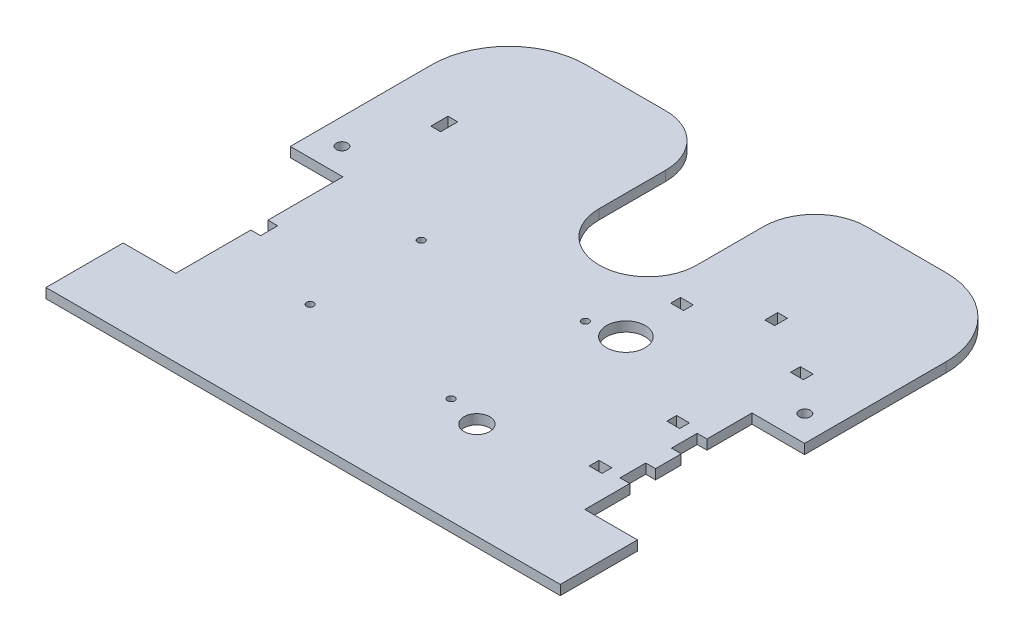
SolidWorks part; units mm, degrees
ref_plane "Front Plane" through (0, 0, 0) normal (0, 0, 1) x (1, 0, 0)
ref_plane "Top Plane" through (0, 0, 0) normal (0, 1, 0) x (1, 0, 0)
ref_plane "Right Plane" through (0, 0, 0) normal (1, 0, 0) x (0, 0, -1)
sketch "Sketch1" plane through (0, 0, 0) normal (0, 1, 0) x (1, 0, 0)
  line L1 (-127, 114.3) -> (127, 114.3)
  line L2 (-127, 114.3) -> (-127, -114.3)
  line L3 (-127, -114.3) -> (127, -114.3)
  line L4 (127, 114.3) -> (127, -114.3)
  line L5 (-127, 114.3) -> (127, -114.3) construction
  line L6 (-127, -114.3) -> (127, 114.3) construction
  point P0 (0, 0)
  dimension "D1" = 254
  dimension "D2" = 228.6
extrude "Boss-Extrude1" add sketch "Sketch1" along normal blind 4.826
sketch "Sketch2" plane through (0, 4.826, 0) normal (0, 1, 0) x (1, 0, 0)
  line L0 (-127, 114.3) -> (-127, -114.3) construction
  line L1 (-127, 6.35) -> (-101, 6.35)
  line L2 (-127, 6.35) -> (-127, -76.2)
  line L3 (-127, -76.2) -> (-101, -76.2)
  line L4 (-101, 6.35) -> (-101, -76.2)
  line L5 (127, -114.3) -> (127, 114.3) construction
  line L6 (127, 6.35) -> (101, 6.35)
  line L7 (127, 6.35) -> (127, -76.2)
  line L8 (127, -76.2) -> (101, -76.2)
  line L9 (101, 6.35) -> (101, -76.2)
  line L10 (-127, -114.3) -> (127, -114.3) construction
  dimension "D1" = 38.1
  dimension "D2" = 38.1
  dimension "D3" = 82.55
  dimension "D4" = 82.55
  dimension "D5" = 26
  dimension "D6" = 26
extrude "Cut-Extrude1" cut sketch "Sketch2" against normal blind 4.826
sketch "Sketch4" plane through (0, 4.826, 0) normal (0, 1, 0) x (1, 0, 0)
  line L0 (0, -114.3) -> (0, 114.3) construction
  line L1 (-127, -114.3) -> (127, -114.3) construction
  line L2 (127, 114.3) -> (-127, 114.3) construction
  line L3 (-127, 76.2) -> (-88.9, 76.2) construction
  line L4 (-127, 114.3) -> (-127, 6.35) construction
  line L5 (-88.9, 76.2) -> (-88.9, 114.3) construction
  line L6 (-127, 76.2) -> (-127, 114.3)
  line L7 (-127, 114.3) -> (-88.9, 114.3)
  line L8 (127, 76.2) -> (127, 114.3)
  line L9 (127, 114.3) -> (88.9, 114.3)
  arc A0 (-127, 76.2) -> (-88.9, 114.3) centre (-88.9, 76.2) cw
  arc A1 (127, 76.2) -> (88.9, 114.3) centre (88.9, 76.2) ccw
  dimension "D1" = 38.1
  dimension "D2" = 38.1
extrude "Cut-Extrude3" cut sketch "Sketch4" against normal blind 4.826
sketch "Sketch17" plane through (0, 0, 0) normal (0, -1, 0) x (1, 0, 0)
  circle A0 centre (114.3, -19.1646) radius 2.7781 construction
  circle A1 centre (-114.3, -19.1646) radius 2.7781 construction
  circle A2 centre (114.3, -19.1646) radius 2.7781
  circle A3 centre (-114.3, -19.1646) radius 2.7781
extrude "Cut-Extrude14" cut sketch "Sketch17" against normal through all
sketch "Sketch18" plane through (0, 4.826, 0) normal (0, 1, 0) x (1, 0, 0)
  line L0 (101, -53.975) -> (96.174, -53.975) construction
  line L1 (96.174, -41.275) -> (96.174, -53.975) construction
  line L2 (101, -41.275) -> (96.174, -41.275) construction
  line L3 (101, -41.275) -> (101, -53.975) construction
  line L4 (101, -15.875) -> (101, -28.575) construction
  line L5 (101, -15.875) -> (96.174, -15.875) construction
  line L6 (96.174, -15.875) -> (96.174, -28.575) construction
  line L7 (101, -28.575) -> (96.174, -28.575) construction
  line L8 (101, -53.975) -> (96.174, -53.975)
  line L9 (96.174, -41.275) -> (96.174, -53.975)
  line L10 (101, -41.275) -> (96.174, -41.275)
  line L11 (101, -41.275) -> (101, -53.975)
  line L12 (101, -15.875) -> (101, -28.575)
  line L13 (101, -15.875) -> (96.174, -15.875)
  line L14 (96.174, -15.875) -> (96.174, -28.575)
  line L15 (101, -28.575) -> (96.174, -28.575)
extrude "Cut-Extrude15" cut sketch "Sketch18" against normal through all
sketch "Sketch19" plane through (0, 4.826, 0) normal (0, 1, 0) x (1, 0, 0)
  line L0 (-101, -39.1583) -> (-101, -30.6917) construction
  line L1 (-101, -39.1583) -> (-96.174, -39.1583) construction
  line L2 (-96.174, -39.1583) -> (-96.174, -30.6917) construction
  line L3 (-101, -30.6917) -> (-96.174, -30.6917) construction
  line L4 (-101, 49.7417) -> (-101, 58.2083) construction
  line L5 (-101, 49.7417) -> (-96.174, 49.7417) construction
  line L6 (-96.174, 49.7417) -> (-96.174, 58.2083) construction
  line L7 (-101, 58.2083) -> (-96.174, 58.2083) construction
  line L8 (-101, -39.1583) -> (-101, -30.6917)
  line L9 (-101, -39.1583) -> (-96.174, -39.1583)
  line L10 (-96.174, -39.1583) -> (-96.174, -30.6917)
  line L11 (-101, -30.6917) -> (-96.174, -30.6917)
  line L12 (-101, 49.7417) -> (-101, 58.2083)
  line L13 (-101, 49.7417) -> (-96.174, 49.7417)
  line L14 (-96.174, 49.7417) -> (-96.174, 58.2083)
  line L15 (-101, 58.2083) -> (-96.174, 58.2083)
extrude "Cut-Extrude16" cut sketch "Sketch19" against normal through all
sketch "Sketch20" plane through (0, 0, 0) normal (0, -1, 0) x (1, 0, 0)
  line L0 (83.474, 51.689) -> (89.824, 51.689) construction
  line L1 (83.474, 56.515) -> (83.474, 51.689) construction
  line L2 (83.474, 56.515) -> (89.824, 56.515) construction
  line L3 (89.824, 56.515) -> (89.824, 51.689) construction
  line L4 (83.474, 13.335) -> (89.824, 13.335) construction
  line L5 (83.474, 18.161) -> (83.474, 13.335) construction
  line L6 (83.474, 18.161) -> (89.824, 18.161) construction
  line L7 (89.824, 18.161) -> (89.824, 13.335) construction
  line L8 (83.474, 51.689) -> (89.824, 51.689)
  line L9 (83.474, 56.515) -> (83.474, 51.689)
  line L10 (83.474, 56.515) -> (89.824, 56.515)
  line L11 (89.824, 56.515) -> (89.824, 51.689)
  line L12 (83.474, 13.335) -> (89.824, 13.335)
  line L13 (83.474, 18.161) -> (83.474, 13.335)
  line L14 (83.474, 18.161) -> (89.824, 18.161)
  line L15 (89.824, 18.161) -> (89.824, 13.335)
extrude "Cut-Extrude17" cut sketch "Sketch20" against normal blind 4.826
sketch "Sketch21" plane through (0, 4.826, 0) normal (0, 1, 0) x (1, 0, 0)
  circle A0 centre (-54.5489, -56.294) radius 1.778 construction
  circle A1 centre (-54.5489, -1.43) radius 1.778 construction
  circle A2 centre (20.6351, -61.882) radius 1.778 construction
  circle A3 centre (20.6351, 4.412) radius 1.778 construction
  circle A4 centre (-54.5489, -56.294) radius 1.778
  circle A5 centre (-54.5489, -1.43) radius 1.778
  circle A6 centre (20.6351, -61.882) radius 1.778
  circle A7 centre (20.6351, 4.412) radius 1.778
extrude "Cut-Extrude18" cut sketch "Sketch21" against normal through all
sketch "Sketch22" plane through (0, 4.826, 0) normal (0, 1, 0) x (1, 0, 0)
  circle A0 centre (37.849, -66.3327) radius 6.35
  circle A1 centre (20.6351, -61.882) radius 1.778 construction
  dimension "D1" = 12.7
  dimension "D2" = 17.78
extrude "Cut-Extrude19" cut sketch "Sketch22" against normal through all
sketch "Sketch24" plane through (0, 0, 0) normal (0, -1, 0) x (1, 0, 0)
  circle A0 centre (0, -55.982) radius 24.13 construction
  circle A1 centre (0, -55.982) radius 24.13
extrude "Cut-Extrude21" cut sketch "Sketch24" against normal through all
sketch "Sketch26" plane through (0, 4.826, 0) normal (0, 1, 0) x (1, 0, 0)
  line L0 (99.476, 38.1) -> (93.126, 38.1) construction
  line L1 (99.476, 38.1) -> (93.126, 38.1)
  line L2 (93.126, 33.274) -> (93.126, 38.1) construction
  line L3 (99.476, 33.274) -> (93.126, 33.274) construction
  line L4 (99.476, 33.274) -> (99.476, 38.1) construction
  line L5 (64.424, 49.276) -> (69.25, 49.276) construction
  line L6 (64.424, 55.626) -> (64.424, 49.276) construction
  line L7 (64.424, 55.626) -> (69.25, 55.626) construction
  line L8 (69.25, 55.626) -> (69.25, 49.276) construction
  line L9 (33.944, 38.1) -> (40.294, 38.1) construction
  line L10 (33.944, 38.1) -> (33.944, 33.274) construction
  line L11 (93.126, 33.274) -> (93.126, 38.1)
  line L12 (99.476, 33.274) -> (93.126, 33.274)
  line L13 (99.476, 33.274) -> (99.476, 38.1)
  line L14 (99.476, 38.1) -> (93.126, 38.1)
  line L15 (64.424, 49.276) -> (69.25, 49.276)
  line L16 (64.424, 55.626) -> (64.424, 49.276)
  line L17 (64.424, 55.626) -> (69.25, 55.626)
  line L18 (69.25, 55.626) -> (69.25, 49.276)
  line L19 (33.944, 38.1) -> (40.294, 38.1)
  line L20 (33.944, 38.1) -> (33.944, 33.274)
  line L21 (33.944, 33.274) -> (40.294, 33.274) construction
  line L22 (40.294, 38.1) -> (40.294, 33.274) construction
  line L23 (33.944, 33.274) -> (40.294, 33.274)
  line L24 (40.294, 38.1) -> (40.294, 33.274)
extrude "Cut-Extrude23" cut sketch "Sketch26" against normal through all contours L18 L17 L16 L15 | L24 L19 L20 L23 | L12 L13 L1 L11 region at (96.301, 4.826, -35.687) region at (66.837, 4.826, -52.451) region at (37.119, 4.826, -35.687)
sketch "Sketch28" plane through (0, 4.826, 0) normal (0, 1, 0) x (1, 0, 0)
  line L0 (-24.13, 55.982) -> (-24.13, 114.3)
  line L1 (88.9, 114.3) -> (-88.9, 114.3) construction
  line L2 (24.13, 55.982) -> (24.13, 114.3)
  line L3 (24.13, 114.3) -> (-24.13, 114.3)
  circle A0 centre (0, 55.982) radius 24.13 construction
  circle A1 centre (0, 55.982) radius 24.13
extrude "Cut-Extrude25" cut sketch "Sketch28" against normal through all contours A1 L2 L3 L0 region at (0, 4.826, -94.2484)
fillet "Fillet1" radius 25.4 2 edges at (-24.13, 2.413, -114.3) (24.13, 2.413, -114.3)
sketch "Sketch29" plane through (0, 4.826, 0) normal (0, 1, 0) x (1, 0, 0)
  line L0 (33.944, 33.274) -> (40.294, 33.274) construction
  circle A0 centre (37.2178, 7.874) radius 9.525
  dimension "D1" = 19.05
  dimension "D2" = 25.4
extrude "Cut-Extrude26" cut sketch "Sketch29" against normal through all
equation "\"MDF\"= 0.19in"
equation "\"GenDiameter\"= 60mm"
equation "\"GenCutDiameter\" = 1.8in"
equation "\"GenCutDistance\" = 1"
equation "\"TowerHeight\" = 6in"
equation "\"TowerFrontBase\" = 3in"
equation "\"FunnelHeight\" = 1in"
equation "\"FunnelAngle\" = 20"
equation "\"TowerSideBase\" = 3in"
equation "\"BaseLength\" = 9in"
equation "\"BaseWidth\" = 10in"
equation "\"WheelHoleLength\" = 3.25in"
equation "\"WheelHoleWidth\" = 26mm"
equation "\"DropLength\" = 1in"
equation "\"D1@Sketch1\"=\"BaseWidth\""
equation "\"D2@Sketch1\"=\"BaseLength\""
equation "\"D1@Boss-Extrude1\"=\"MDF\""
equation "\"WheelHoleFromBack\" = 1.5in"
equation "\"D1@Sketch2\"=\"WheelHoleFromBack\""
equation "\"D2@Sketch2\"=\"WheelHoleFromBack\""
equation "\"D3@Sketch2\"=\"WheelHoleLength\""
equation "\"D4@Sketch2\"=\"WheelHoleLength\""
equation "\"D5@Sketch2\"=\"WheelHoleWidth\""
equation "\"D6@Sketch2\"=\"WheelHoleWidth\""
equation "\"D1@Cut-Extrude1\"=\"MDF\""
equation "\"DropWidth\" = 8.5in"
equation "\"BumperWidth\" = 2in"
equation "\"D1@Cut-Extrude3\"=\"MDF\""
equation "\"DropWidthTop\" = 0in"
equation "\"D1@Cut-Extrude17\"=\"MDF\""
